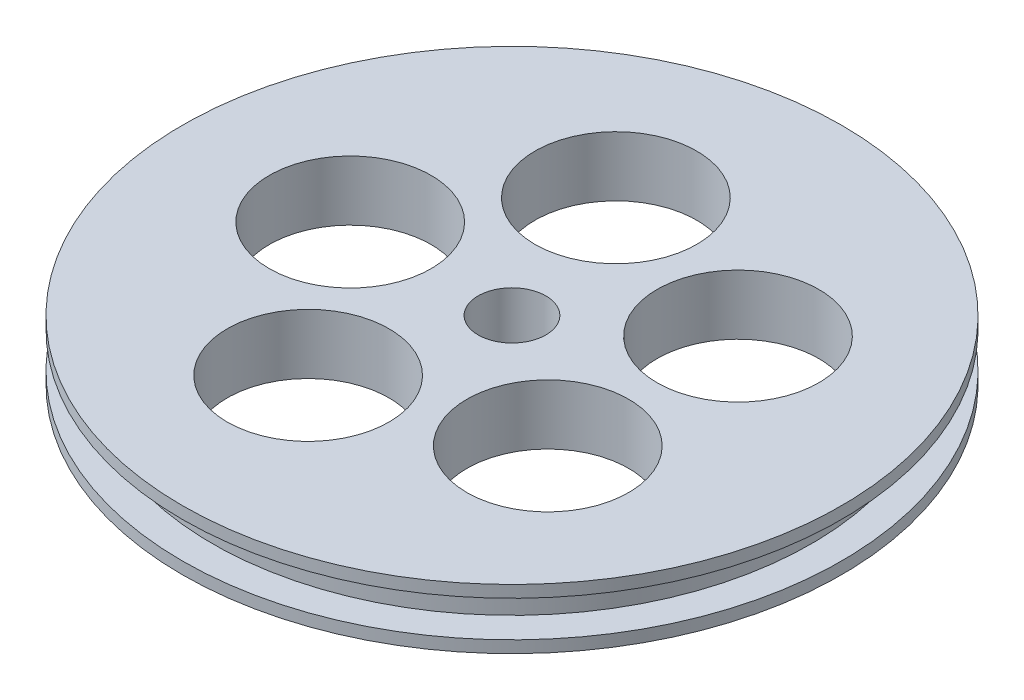
SolidWorks part; units mm, degrees
ref_plane "Front Plane" through (0, 0, 0) normal (0, 0, 1) x (1, 0, 0)
ref_plane "Top Plane" through (0, 0, 0) normal (0, 1, 0) x (1, 0, 0)
ref_plane "Right Plane" through (0, 0, 0) normal (1, 0, 0) x (0, 0, -1)
sketch "Sketch1" plane through (0, 0, 0) normal (1, 0, 0) x (0, 0, -1)
  line L0 (0, 3) -> (-5, 3) construction
  line L1 (0, 0) -> (50, 0)
  line L2 (0, 0) -> (0, -2)
  line L3 (0, -2) -> (50, -2)
  line L4 (50, 0) -> (50, -2)
  line L5 (0, 0) -> (45, 0)
  line L6 (0, 0) -> (0, 6)
  line L7 (0, 6) -> (45, 6)
  line L8 (45, 0) -> (45, 6)
  line L9 (0, 6) -> (50, 6)
  line L10 (0, 6) -> (0, 8)
  line L11 (0, 8) -> (50, 8)
  line L12 (50, 6) -> (50, 8)
  line L13 (-5, 3) -> (-5, 20.5021) construction
  dimension "D1" = 2
  dimension "D2" = 6
  dimension "D3" = 50
  dimension "D4" = 45
  dimension "D5" = 5
revolve "Revolve4" add sketch "Sketch1" angle 360 about L13 region at (0, 3, -22.5) region at (0, -1, -25) region at (0, 7, -25)
sketch "Sketch3" plane through (0, 8, 0) normal (0, 1, 0) x (1, 0, 0)
  circle A0 centre (0, -5) radius 5.6537
  circle A1 centre (0, -5) radius 5 construction
  circle A2 centre (-27, -5) radius 13.5
  circle A3 centre (-8.3435, 20.6785) radius 13.5
  circle A4 centre (21.8435, 10.8702) radius 13.5
  circle A5 centre (21.8435, -20.8702) radius 13.5
  circle A6 centre (-8.3435, -30.6785) radius 13.5
  point P17 (0, -5)
  dimension "D2" = 27
  dimension "D1" = 27
  dimension "D3" = 5
extrude "Cut-Extrude1" cut sketch "Sketch3" against normal blind 10
